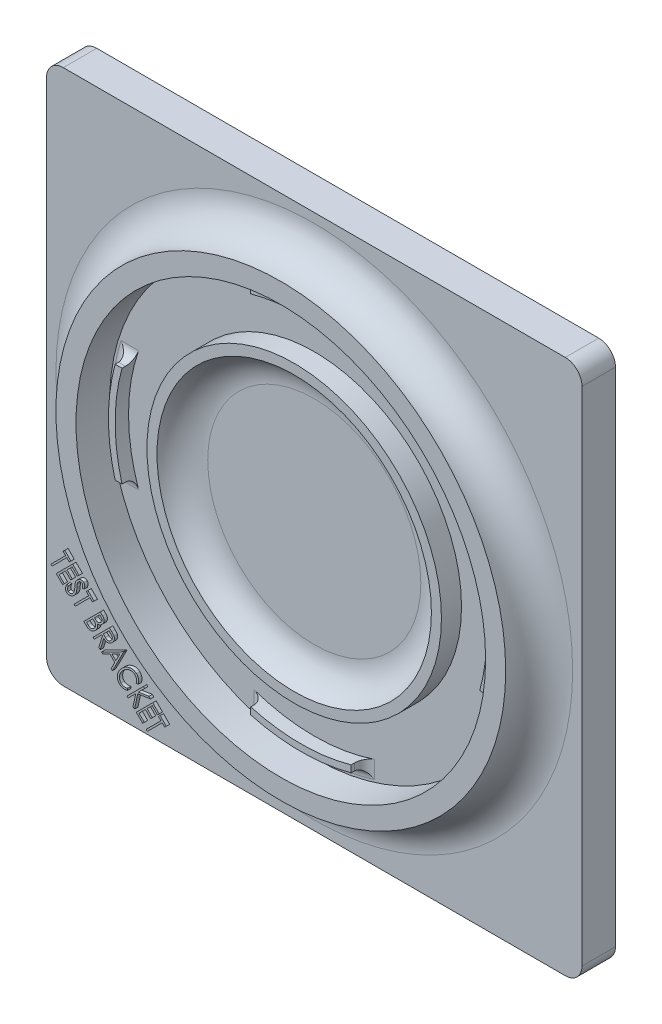
SolidWorks part; units mm, degrees
ref_plane "Front Plane" through (0, 0, 0) normal (0, 0, 1) x (1, 0, 0)
ref_plane "Top Plane" through (0, 0, 0) normal (0, 1, 0) x (1, 0, 0)
ref_plane "Right Plane" through (0, 0, 0) normal (1, 0, 0) x (0, 0, -1)
sketch "Sketch1" plane through (0, 0, 0) normal (0, 0, 1) x (1, 0, 0)
  line L1 (-40, 40) -> (40, 40)
  line L2 (-40, 40) -> (-40, -40)
  line L3 (-40, -40) -> (40, -40)
  line L4 (40, 40) -> (40, -40)
  line L5 (-40, 40) -> (40, -40) construction
  line L6 (-40, -40) -> (40, 40) construction
  point P0 (0, 0)
  dimension "D1" = 80
  dimension "D2" = 80
extrude "Boss-Extrude1" add sketch "Sketch1" along normal blind 5
sketch "Sketch5" plane through (0, 0, 5) normal (0, 0, 1) x (1, 0, 0)
  line L5 (0, 29) -> (0, 27.75) construction
  line L6 (-7.5, 29) -> (7.5, 29)
  line L11 (-7.5, 29) -> (-7.5, -29)
  line L12 (-7.5, -29) -> (7.5, -29)
  line L16 (7.5, 29) -> (7.5, -29)
  line L17 (-7.5, 29) -> (7.5, -29) construction
  line L18 (-7.5, -29) -> (7.5, 29) construction
  line L19 (-29, 7.5) -> (29, 7.5)
  line L20 (-29, 7.5) -> (-29, -7.5)
  line L21 (-29, -7.5) -> (29, -7.5)
  line L22 (29, 7.5) -> (29, -7.5)
  line L23 (-29, 7.5) -> (29, -7.5) construction
  line L24 (-29, -7.5) -> (29, 7.5) construction
  line L26 (-2, 29.0722) -> (2, 29.0722)
  line L27 (-2, 29.0722) -> (-2, 27.6778)
  line L28 (-2, 27.6778) -> (2, 27.6778)
  line L29 (2, 29.0722) -> (2, 27.6778)
  line L30 (-2, 29.0722) -> (2, 27.6778) construction
  line L31 (-2, 27.6778) -> (2, 29.0722) construction
  circle A8 centre (0, 0) radius 27.75
  circle A9 centre (0, 0) radius 28.75
  point P14 (0, 28.375)
  dimension "D1" = 57.5
  dimension "D2" = 55.5
  dimension "D3" = 15
  dimension "D4" = 58
  dimension "D5" = 15
  dimension "D6" = 58
  dimension "D7" = 4
extrude "Boss-Extrude2" add sketch "Sketch5" along normal blind 2 contours L19 A9 L21 A8 | L27 A9 L11 A8 | L16 A9 L29 A8 | A9 L19 A8 L21 | L11 A9 L16 A8 region at (-4.7656, 27.7983, 5) region at (-27.9111, 0, 5) region at (4.7656, 27.7983, 5) region at (0, -27.9111, 5) region at (27.9111, 0, 5)
sketch "Sketch12" plane through (0, 0, 5) normal (0, 0, 1) x (1, 0, 0)
  circle A0 centre (0, 0) radius 30.6
  circle A1 centre (0, 0) radius 33.6
  dimension "D1" = 61.2
  dimension "D2" = 67.2
extrude "Boss-Extrude3" add sketch "Sketch12" along normal blind 5
sketch "Sketch13" plane through (0, 0, 5) normal (0, 0, 1) x (1, 0, 0)
  circle A0 centre (0, 0) radius 20.5
  circle A1 centre (0, 0) radius 22
  dimension "D1" = 44
  dimension "D2" = 41
extrude "Boss-Extrude4" add sketch "Sketch13" along normal blind 3
sketch "Sketch14" plane through (0, 0, 5) normal (0, 0, 1) x (1, 0, 0)
  line L0 (-39.2678, -24.2678) -> (-24.2678, -39.2678) construction
  text T0 "TEST BRACKET" font "Century Gothic" height 3.5
extrude "Boss-Extrude5" add sketch "Sketch14" along normal blind 0.5
fillet "Fillet1" radius 2.5 4 edges at (40, 40, 2.5) (-40, 40, 2.5) (40, -40, 2.5) (-40, -40, 2.5)
fillet "Fillet2" radius 1.5 15 edges at (28.75, 0, 5) (0, -28.75, 5) (-28.75, 0, 5) (4.7725, 28.3511, 5) (-4.7725, 28.3511, 5) (7.5, -27.2359, 5) (-7.5, -27.2359, 5) (-27.2359, -7.5, 5) (-27.2359, 7.5, 5) (27.2359, 7.5, 5) (27.2359, -7.5, 5) (7.5, 27.2359, 5) (2, 28.1791, 5) (-2, 28.1791, 5) (-7.5, 27.2359, 5)
fillet "Fillet3" radius 5 2 edges at (33.6, 0, 5) (20.5, 0, 5)
